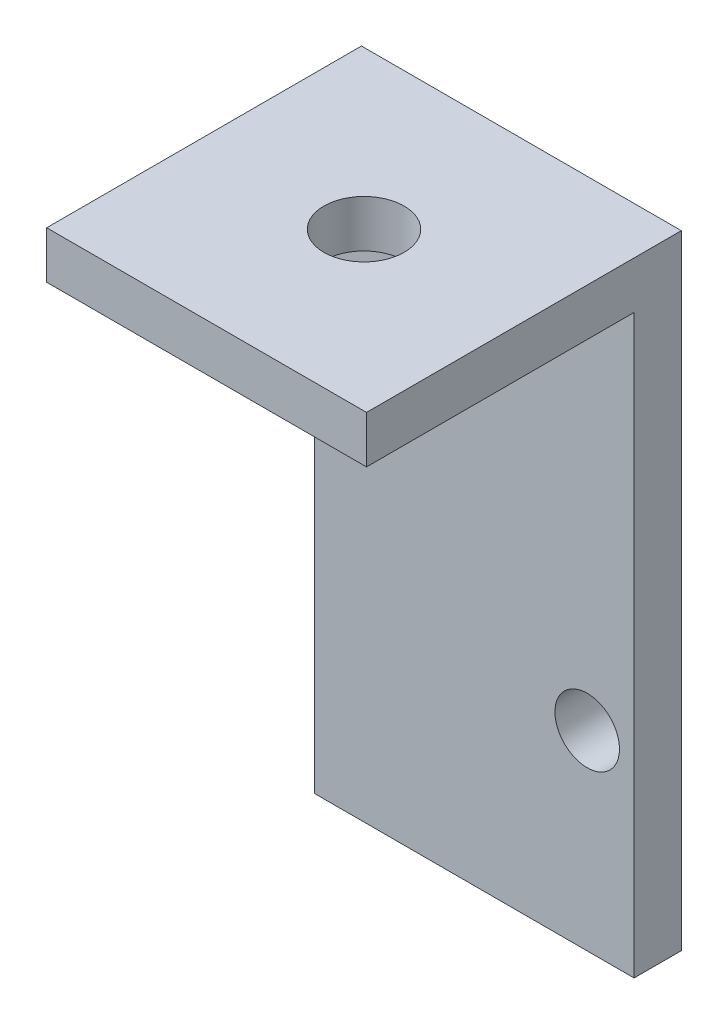
SolidWorks part; units mm, degrees
ref_plane "Front Plane" through (0, 0, 0) normal (0, 0, 1) x (1, 0, 0)
ref_plane "Top Plane" through (0, 0, 0) normal (0, 1, 0) x (1, 0, 0)
ref_plane "Right Plane" through (0, 0, 0) normal (1, 0, 0) x (0, 0, -1)
sketch "Sketch1" plane through (0, 0, 0) normal (0, 0, 1) x (1, 0, 0)
  line L0 (0, 36.62) -> (20.32, 36.62) construction
  line L1 (0, 0) -> (20.32, 0)
  line L2 (0, 0) -> (0, 39.62)
  line L3 (0, 39.62) -> (20.32, 39.62)
  line L4 (20.32, 0) -> (20.32, 39.62)
  circle A0 centre (17.34, 12.13) radius 2.05
  circle A1 centre (2.99, 34.1) radius 2.05
  dimension "D6" = 4.1
  dimension "D1" = 20.32
  dimension "D2" = 39.62
  dimension "D3" = 3
  dimension "D4" = 17.33
  dimension "D5" = 2.98
  dimension "D7" = 34.1
  dimension "D8" = 12.13
extrude "Boss-Extrude1" add sketch "Sketch1" along normal blind 3
sketch "Sketch2" plane through (0, 39.62, 0) normal (0, 1, 0) x (1, 0, 0)
  line L0 (0, 0) -> (20.32, 0) construction
  line L1 (0, -3) -> (20.32, -3)
  line L2 (0, -3) -> (0, -20)
  line L3 (0, -20) -> (20.32, -20)
  line L4 (20.32, -3) -> (20.32, -20)
  line L5 (10.16, -20) -> (10.16, 0) construction
  circle A0 centre (10.16, -10) radius 2.55
  point P11 (10.16, 0)
  dimension "D2" = 5.1
  dimension "D1" = 20
extrude "Boss-Extrude2" add sketch "Sketch2" against normal up to vertex (3 mm away) up to point (0, 36.62, 0)
